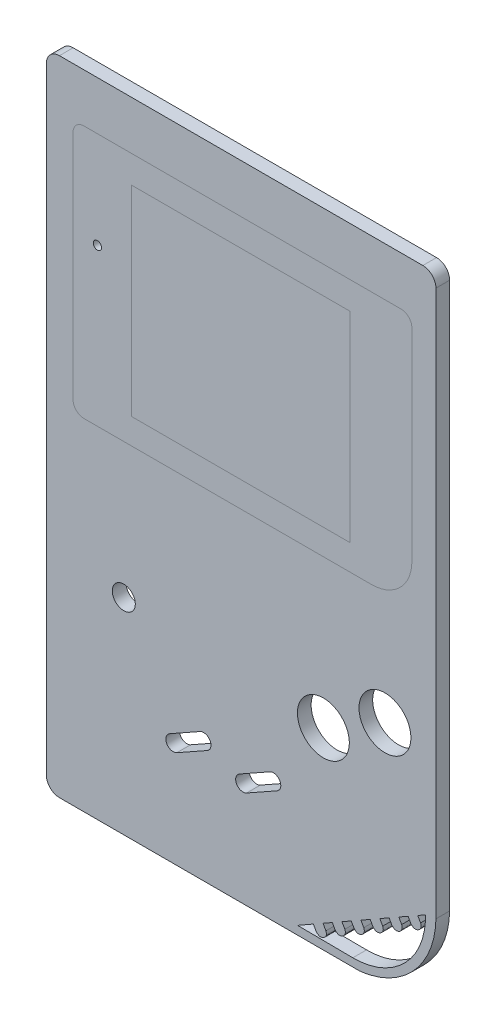
SolidWorks part; units mm, degrees
ref_plane "Front Plane" through (0, 0, 0) normal (0, 0, 1) x (1, 0, 0)
ref_plane "Top Plane" through (0, 0, 0) normal (0, 1, 0) x (1, 0, 0)
ref_plane "Right Plane" through (0, 0, 0) normal (1, 0, 0) x (0, 0, -1)
sketch "Sketch1" plane through (0, 0, 0) normal (0, 0, 1) x (1, 0, 0)
  line L1 (-26.2308, 73.6471) -> (38.6518, 73.6471)
  line L3 (-44.6471, -70.649) -> (-44.6471, 70.649)
  line L5 (27.0934, -73.6471) -> (-41.649, -73.6471)
  line L7 (-24.0867, 73.6955) -> (-35.6911, 73.6955)
  line L15 (-16.3293, -29.1587) -> (-16.3293, -23.8757)
  line L19 (44.6471, 67.6705) -> (44.6471, -53.896)
  line L20 (-0.4012, -48.3225) -> (6.5714, -44.4005)
  line L21 (8.2266, -47.343) -> (1.254, -51.2651)
  line L22 (-44.6471, 73.6471) -> (44.6471, 73.6471)
  line L23 (44.6471, 73.6471) -> (44.6471, -73.6471)
  line L24 (44.6471, -73.6471) -> (-44.6471, -73.6471)
  line L25 (-44.6471, -73.6471) -> (-44.6471, 73.6471)
  line L26 (-25.1679, 56.2163) -> (-25.1679, 10.288)
  line L27 (-25.1679, 10.288) -> (24.9222, 10.288)
  line L28 (24.9222, 10.288) -> (24.9222, 56.2163)
  line L29 (24.9222, 56.2163) -> (-25.1679, 56.2163)
  line L34 (36.6393, 62.5051) -> (-36.0272, 62.5051)
  line L35 (-38.5272, 60.0051) -> (-38.5272, 6.9331)
  line L36 (-36.0272, 4.4331) -> (29.8893, 4.4331)
  line L37 (39.1393, 13.6831) -> (39.1393, 60.0051)
  line L38 (-16.4012, -48.3225) -> (-9.4286, -44.4005)
  line L39 (-7.7734, -47.343) -> (-14.746, -51.2651)
  line L41 (44.6471, 70.649) -> (44.6471, 67.6705)
  line L43 (38.6518, 73.6471) -> (41.649, 73.6471)
  line L45 (-41.649, 73.6471) -> (-26.2308, 73.6471)
  line L86 (-41.649, -70.649) -> (-10.3129, -70.649)
  line L87 (-8.1987, -68.3681) -> (3.0521, -68.3681)
  line L88 (5.1532, -70.649) -> (12.3245, -70.649)
  line L89 (12.3245, -70.649) -> (15.9618, -68.571)
  line L90 (15.9618, -68.571) -> (10.9804, -59.6626)
  line L91 (13.2009, -58.4087) -> (18.176, -67.306)
  line L92 (18.176, -67.306) -> (20.3032, -66.0908)
  line L93 (20.3032, -66.0908) -> (15.3219, -57.1823)
  line L94 (17.5423, -55.9285) -> (22.5175, -64.8258)
  line L95 (22.5175, -64.8258) -> (24.6447, -63.6105)
  line L96 (24.6447, -63.6105) -> (19.6633, -54.7021)
  line L97 (21.8838, -53.4482) -> (26.8589, -62.3455)
  line L98 (26.8589, -62.3455) -> (28.9862, -61.1302)
  line L99 (28.9862, -61.1302) -> (24.0048, -52.2218)
  line L100 (26.2253, -50.968) -> (31.2004, -59.8653)
  line L101 (31.2004, -59.8653) -> (33.3276, -58.65)
  line L102 (33.3276, -58.65) -> (28.3462, -49.7415)
  line L103 (30.5667, -48.4877) -> (35.5419, -57.385)
  line L104 (35.5419, -57.385) -> (37.6691, -56.1697)
  line L105 (37.6691, -56.1697) -> (32.6877, -47.2613)
  line L106 (34.9082, -46.0074) -> (39.8833, -54.9047)
  line L107 (39.8833, -54.9047) -> (41.649, -53.896)
  line L108 (41.649, -53.896) -> (41.649, 65.7705)
  line L109 (41.649, 65.7705) -> (-41.649, 65.7705)
  line L110 (-41.649, 65.7705) -> (-41.649, -70.649)
  line L132 (38.9077, -58.3876) -> (38.2613, -57.2293)
  line L133 (38.2613, -57.2293) -> (36.134, -58.4446)
  line L134 (36.134, -58.4446) -> (36.7862, -59.6131)
  line L135 (34.5662, -60.8679) -> (33.9198, -59.7095)
  line L136 (33.9198, -59.7095) -> (31.7926, -60.9248)
  line L137 (31.7926, -60.9248) -> (32.4447, -62.0934)
  line L138 (30.2248, -63.3482) -> (29.5783, -62.1898)
  line L139 (29.5783, -62.1898) -> (27.4511, -63.4051)
  line L140 (27.4511, -63.4051) -> (28.1032, -64.5736)
  line L141 (25.8833, -65.8284) -> (25.2369, -64.6701)
  line L142 (25.2369, -64.6701) -> (23.1097, -65.8853)
  line L143 (23.1097, -65.8853) -> (23.7618, -67.0539)
  line L144 (21.5418, -68.3087) -> (20.8954, -67.1503)
  line L145 (20.8954, -67.1503) -> (18.7682, -68.3656)
  line L146 (18.7682, -68.3656) -> (19.4203, -69.5342)
  line L147 (17.2004, -70.7889) -> (16.554, -69.6306)
  line L148 (16.554, -69.6306) -> (12.9266, -71.7029)
  line L149 (12.9266, -71.7029) -> (25.6021, -71.8013)
  line L150 (42.2525, -55.0539) -> (42.2511, -54.9499)
  line L151 (42.2511, -54.9499) -> (40.4755, -55.9643)
  line L152 (40.4755, -55.9643) -> (41.1276, -57.1329)
  circle A0 centre (34.1495, 24.0914) radius 10.7
  circle A2 centre (-26.9008, -26.5172) radius 2.6415
  arc A3 (8.2266, -47.343) -> (6.5714, -44.4005) centre (7.399, -45.8717) ccw
  arc A6 (-16.4012, -48.3225) -> (-14.746, -51.2651) centre (-15.5736, -49.7938) ccw
  arc A7 (-7.7734, -47.343) -> (-9.4286, -44.4005) centre (-8.601, -45.8717) ccw
  circle A15 centre (18.8495, -29.5462) radius 5.95
  circle A16 centre (32.9602, -21.4767) radius 5.95
  arc A17 (-0.4012, -48.3225) -> (1.254, -51.2651) centre (0.4264, -49.7938) ccw
  circle A19 centre (-32.9539, 40.3411) radius 0.9464
  arc A24 (39.1393, 60.0051) -> (36.6393, 62.5051) centre (36.6393, 60.0051) ccw
  arc A25 (-36.0272, 62.5051) -> (-38.5272, 60.0051) centre (-36.0272, 60.0051) ccw
  arc A26 (-38.5272, 6.9331) -> (-36.0272, 4.4331) centre (-36.0272, 6.9331) ccw
  arc A27 (29.8893, 4.4331) -> (39.1393, 13.6831) centre (29.8893, 13.6831) ccw
  ellipse E2 centre (25.7287, -55.2756) end of major axis (33.9268, -69.6256) minor radius 16.5247 (25.6021, -71.8013) -> (42.2525, -55.0539) ccw
  ellipse E3 centre (-41.649, -70.649) end of major axis (-39.5276, -72.7703) minor radius 2.9963 (-44.6471, -70.649) -> (-41.649, -73.6471) ccw
  ellipse E5 centre (41.649, 70.649) end of major axis (39.5276, 72.7703) minor radius 2.9963 (44.6471, 70.649) -> (41.649, 73.6471) ccw
  ellipse E7 centre (-41.649, 70.649) end of major axis (-43.7703, 68.5276) minor radius 2.9963 (-41.649, 73.6471) -> (-44.6471, 70.649) ccw
  spline S1 degree 3 poles (44.6485, -54) (44.663, -55.258) (44.5568, -56.5068) (44.2157, -58.3662) (44.0715, -58.9837) (43.7192, -60.2138) (43.5128, -60.8202) (42.8075, -62.6008) (42.2221, -63.7422) (41.3373, -65.1085) (41.1525, -65.3788) (40.7717, -65.907) (40.5751, -66.1657) (39.9672, -66.9256) (39.1083, -67.8961) (38.1523, -68.7812) (37.1464, -69.6222) (36.6152, -70.0225) (34.9811, -71.1285) (33.8311, -71.748) (32.3187, -72.3766) (32.0124, -72.495) (31.3922, -72.7168) (31.0776, -72.8204) (30.1333, -73.105) (29.5001, -73.2613) (27.5898, -73.6337) (26.302, -73.7542) (25, -73.7456) knots 0 0 0 0 0.125 0.125 0.1875 0.1875 0.25 0.25 0.375 0.375 0.40625 0.40625 0.4375 0.4375 0.5 0.5625 0.5625 0.625 0.625 0.75 0.75 0.78125 0.78125 0.8125 0.8125 0.875 0.875 1 1 1 1
  spline S16 degree 2 poles (-10.3129, -70.649) (-10.2959, -70.0915) (-10.2006, -69.7936) (-10.0641, -69.3669) (-9.759, -69.0489) (-9.459, -68.7361) (-9.0409, -68.5758) (-8.7904, -68.4798) (-8.1987, -68.3681) knots 0 0 0 0.25 0.25 0.5 0.5 0.75 0.75 1 1 1
  spline S17 degree 2 poles (3.0521, -68.3681) (3.5991, -68.4314) (3.8948, -68.5497) (4.2959, -68.7102) (4.5973, -69.0441) (4.8867, -69.3648) (5.0109, -69.7992) (5.0923, -70.0841) (5.1532, -70.649) knots 0 0 0 0.25 0.25 0.5 0.5 0.75 0.75 1 1 1
  spline S18 degree 3 poles (10.9804, -59.6626) (10.9237, -59.5079) (10.8663, -59.3527) (10.8275, -59.1078) (10.823, -59.0261) (10.8338, -58.8627) (10.8488, -58.7804) (10.9175, -58.5442) (10.9958, -58.3954) (11.1989, -58.1385) (11.3277, -58.0278) (11.6113, -57.866) (11.7701, -57.8104) (12.093, -57.7637) (12.2617, -57.7725) (12.5753, -57.8739) (12.7158, -57.9628) (12.9713, -58.1722) (13.0857, -58.2909) (13.2009, -58.4087) knots 0 0 0 0 0.125 0.125 0.1875 0.1875 0.25 0.25 0.375 0.375 0.5 0.5 0.625 0.625 0.75 0.75 0.875 0.875 1 1 1 1
  spline S19 degree 3 poles (15.3219, -57.1823) (15.2651, -57.0276) (15.2078, -56.8724) (15.169, -56.6275) (15.1645, -56.5458) (15.1753, -56.3824) (15.1903, -56.3001) (15.259, -56.0639) (15.3373, -55.9151) (15.5404, -55.6582) (15.6691, -55.5475) (15.9527, -55.3857) (16.1115, -55.3301) (16.4345, -55.2834) (16.6032, -55.2923) (16.9168, -55.3936) (17.0573, -55.4826) (17.3128, -55.6919) (17.4272, -55.8106) (17.5423, -55.9285) knots 0 0 0 0 0.125 0.125 0.1875 0.1875 0.25 0.25 0.375 0.375 0.5 0.5 0.625 0.625 0.75 0.75 0.875 0.875 1 1 1 1
  spline S20 degree 3 poles (19.6633, -54.7021) (19.6066, -54.5474) (19.5492, -54.3921) (19.5105, -54.1473) (19.506, -54.0656) (19.5167, -53.9022) (19.5318, -53.8198) (19.6004, -53.5837) (19.6788, -53.4349) (19.8818, -53.1779) (20.0106, -53.0673) (20.2942, -52.9055) (20.453, -52.8499) (20.7759, -52.8032) (20.9446, -52.812) (21.2583, -52.9134) (21.3988, -53.0023) (21.6542, -53.2117) (21.7686, -53.3303) (21.8838, -53.4482) knots 0 0 0 0 0.125 0.125 0.1875 0.1875 0.25 0.25 0.375 0.375 0.5 0.5 0.625 0.625 0.75 0.75 0.875 0.875 1 1 1 1
  spline S21 degree 3 poles (24.0048, -52.2218) (23.9481, -52.0671) (23.8907, -51.9119) (23.8519, -51.667) (23.8474, -51.5853) (23.8582, -51.4219) (23.8732, -51.3396) (23.9419, -51.1034) (24.0202, -50.9546) (24.2233, -50.6977) (24.3521, -50.587) (24.6357, -50.4252) (24.7945, -50.3696) (25.1174, -50.3229) (25.2861, -50.3318) (25.5997, -50.4331) (25.7402, -50.5221) (25.9957, -50.7314) (26.1101, -50.8501) (26.2253, -50.968) knots 0 0 0 0 0.125 0.125 0.1875 0.1875 0.25 0.25 0.375 0.375 0.5 0.5 0.625 0.625 0.75 0.75 0.875 0.875 1 1 1 1
  spline S22 degree 3 poles (28.3462, -49.7415) (28.2895, -49.5868) (28.2322, -49.4316) (28.1934, -49.1867) (28.1889, -49.1051) (28.1997, -48.9416) (28.2147, -48.8593) (28.2834, -48.6232) (28.3617, -48.4744) (28.5648, -48.2174) (28.6935, -48.1067) (28.9771, -47.9449) (29.1359, -47.8893) (29.4589, -47.8427) (29.6275, -47.8515) (29.9412, -47.9529) (30.0817, -48.0418) (30.3372, -48.2512) (30.4516, -48.3698) (30.5667, -48.4877) knots 0 0 0 0 0.125 0.125 0.1875 0.1875 0.25 0.25 0.375 0.375 0.5 0.5 0.625 0.625 0.75 0.75 0.875 0.875 1 1 1 1
  spline S23 degree 3 poles (32.6877, -47.2613) (32.631, -47.1066) (32.5736, -46.9514) (32.5349, -46.7065) (32.5304, -46.6248) (32.5411, -46.4614) (32.5561, -46.3791) (32.6248, -46.1429) (32.7032, -45.9941) (32.9062, -45.7372) (33.035, -45.6265) (33.3186, -45.4647) (33.4774, -45.4091) (33.8003, -45.3624) (33.969, -45.3712) (34.2826, -45.4726) (34.4232, -45.5615) (34.6786, -45.7709) (34.793, -45.8896) (34.9082, -46.0074) knots 0 0 0 0 0.125 0.125 0.1875 0.1875 0.25 0.25 0.375 0.375 0.5 0.5 0.625 0.625 0.75 0.75 0.875 0.875 1 1 1 1
  spline S30 degree 3 poles (41.1276, -57.1329) (41.1775, -57.2757) (41.2281, -57.4203) (41.2567, -57.6456) (41.2583, -57.7216) (41.2417, -57.8761) (41.224, -57.9529) (41.1485, -58.1757) (41.0665, -58.318) (40.8579, -58.5665) (40.7277, -58.6749) (40.4441, -58.8368) (40.2866, -58.8947) (39.9687, -58.9503) (39.8039, -58.9483) (39.5005, -58.865) (39.3662, -58.787) (39.1238, -58.6005) (39.0161, -58.4937) (38.9077, -58.3876) knots 0 0 0 0 0.125 0.125 0.1875 0.1875 0.25 0.25 0.375 0.375 0.5 0.5 0.625 0.625 0.75 0.75 0.875 0.875 1 1 1 1
  spline S31 degree 3 poles (36.7862, -59.6131) (36.836, -59.7559) (36.8866, -59.9005) (36.9153, -60.1258) (36.9168, -60.2019) (36.9002, -60.3564) (36.8826, -60.4332) (36.807, -60.6559) (36.7251, -60.7982) (36.5164, -61.0468) (36.3863, -61.1551) (36.1027, -61.317) (35.9451, -61.3749) (35.6272, -61.4306) (35.4624, -61.4285) (35.159, -61.3453) (35.0247, -61.2673) (34.7823, -61.0808) (34.6746, -60.974) (34.5662, -60.8679) knots 0 0 0 0 0.125 0.125 0.1875 0.1875 0.25 0.25 0.375 0.375 0.5 0.5 0.625 0.625 0.75 0.75 0.875 0.875 1 1 1 1
  spline S32 degree 3 poles (32.4447, -62.0934) (32.4946, -62.2362) (32.5452, -62.3808) (32.5738, -62.6061) (32.5754, -62.6822) (32.5587, -62.8366) (32.5411, -62.9135) (32.4656, -63.1362) (32.3836, -63.2785) (32.175, -63.527) (32.0448, -63.6354) (31.7612, -63.7973) (31.6037, -63.8552) (31.2858, -63.9108) (31.1209, -63.9088) (30.8176, -63.8255) (30.6832, -63.7475) (30.4408, -63.561) (30.3332, -63.4542) (30.2248, -63.3482) knots 0 0 0 0 0.125 0.125 0.1875 0.1875 0.25 0.25 0.375 0.375 0.5 0.5 0.625 0.625 0.75 0.75 0.875 0.875 1 1 1 1
  spline S33 degree 3 poles (28.1032, -64.5736) (28.1531, -64.7164) (28.2037, -64.861) (28.2324, -65.0864) (28.2339, -65.1624) (28.2173, -65.3169) (28.1996, -65.3937) (28.1241, -65.6165) (28.0421, -65.7587) (27.8335, -66.0073) (27.7033, -66.1156) (27.4197, -66.2775) (27.2622, -66.3354) (26.9443, -66.3911) (26.7795, -66.3891) (26.4761, -66.3058) (26.3418, -66.2278) (26.0994, -66.0413) (25.9917, -65.9345) (25.8833, -65.8284) knots 0 0 0 0 0.125 0.125 0.1875 0.1875 0.25 0.25 0.375 0.375 0.5 0.5 0.625 0.625 0.75 0.75 0.875 0.875 1 1 1 1
  spline S34 degree 3 poles (23.7618, -67.0539) (23.8117, -67.1967) (23.8623, -67.3413) (23.8909, -67.5666) (23.8924, -67.6427) (23.8758, -67.7971) (23.8582, -67.874) (23.7826, -68.0967) (23.7007, -68.239) (23.4921, -68.4876) (23.3619, -68.5959) (23.0783, -68.7578) (22.9207, -68.8157) (22.6029, -68.8713) (22.438, -68.8693) (22.1346, -68.7861) (22.0003, -68.708) (21.7579, -68.5216) (21.6502, -68.4147) (21.5418, -68.3087) knots 0 0 0 0 0.125 0.125 0.1875 0.1875 0.25 0.25 0.375 0.375 0.5 0.5 0.625 0.625 0.75 0.75 0.875 0.875 1 1 1 1
  spline S35 degree 3 poles (19.4203, -69.5342) (19.4702, -69.677) (19.5208, -69.8216) (19.5494, -70.0469) (19.551, -70.1229) (19.5343, -70.2774) (19.5167, -70.3542) (19.4412, -70.577) (19.3592, -70.7193) (19.1506, -70.9678) (19.0204, -71.0762) (18.7368, -71.2381) (18.5793, -71.296) (18.2614, -71.3516) (18.0965, -71.3496) (17.7932, -71.2663) (17.6589, -71.1883) (17.4164, -71.0018) (17.3088, -70.895) (17.2004, -70.7889) knots 0 0 0 0 0.125 0.125 0.1875 0.1875 0.25 0.25 0.375 0.375 0.5 0.5 0.625 0.625 0.75 0.75 0.875 0.875 1 1 1 1
  dimension "D4" = 21.4
  dimension "D1" = 10.4977
  dimension "D2" = 89.2943
  dimension "D3" = 147.2943
extrude "Boss-Extrude1" add sketch "Sketch1" along normal blind 3.14 contours L105 S23 L106 L107 L108 A0 L37 A27 L36 A26 L35 A25 L34 A24 L109 L110 L86 S16 L87 S17 L88 L89 L90 S18 L91 L92 L93 S19 L94 L95 L96 S20 L97 L98 L99 S21 L100 L101 L102 S22 L103 L104 A2 | L108 A0 L37 | S23 L105 L104 L103 S22 L102 L101 L100 S21 L99 L98 L97 S20 L96 L95 L94 S19 L93 L92 L91 S18 L90 L89 L88 S17 L87 S16 L86 L110 L109 L108 A0 L19 L23 E5 L22 L1 E7 L3 E3 L5 S1 L107 L106 S35 | L23 A0 L108 region at (6.2105, 71.9247, 0) region at (42.917, 24.0914, 0) region at (-3.2026, -23.3623, 0) region at (40.3501, 24.0914, 0)
extrude "Boss-Extrude2" add sketch "Sketch1<3>" along normal blind 3.14 separate body contours L36 A27 L37 A0 L28 L27 L26 L29 A24 L34 A25 L35 A26 A19 | L37 A0 L28 region at (30.9538, 35.3151, 0) region at (32.4596, 24.0914, 0)
sketch "Sketch1<3>" plane through (0, 0, 0) normal (0, 0, 1) x (1, 0, 0) same geometry as "Sketch1"
extrude "Boss-Extrude3" add sketch "Sketch1<4>" along normal blind 3.14 separate body contours A0 L28 L29 L26 L27 | L28 A0 region at (-0.2381, 33.2953, 0) region at (24.3295, 24.0914, 0)
sketch "Sketch1<4>" plane through (0, 0, 0) normal (0, 0, 1) x (1, 0, 0) same geometry as "Sketch1"
